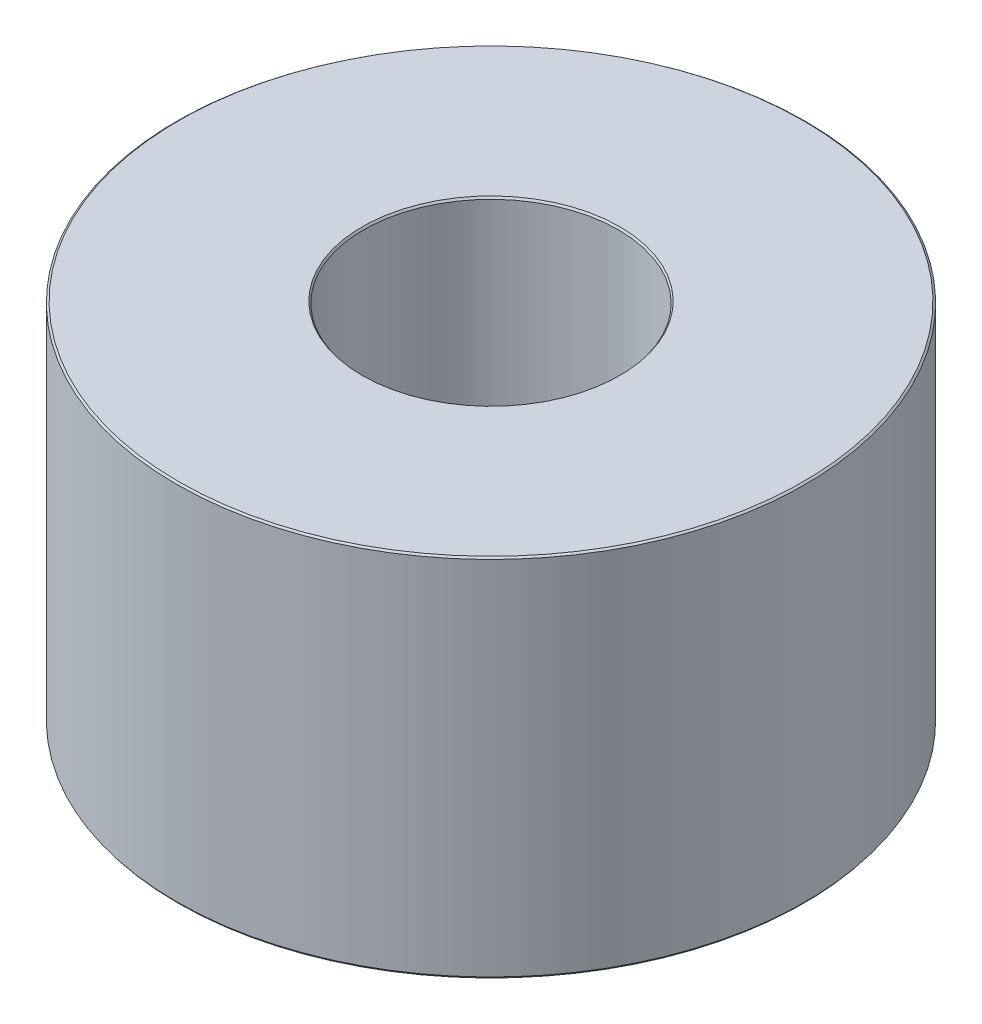
SolidWorks part; units mm, degrees
ref_plane "Front Plane" through (0, 0, 0) normal (0, 0, 1) x (1, 0, 0)
ref_plane "Top Plane" through (0, 0, 0) normal (0, 1, 0) x (1, 0, 0)
ref_plane "Right Plane" through (0, 0, 0) normal (1, 0, 0) x (0, 0, -1)
sketch "Sketch1" plane through (0, 0, 0) normal (0, 1, 0) x (1, 0, 0)
  circle A0 centre (0, 0) radius 47.5
  dimension "SLEEVE_OD" = 95
extrude "Boss-Extrude1" add sketch "Sketch1" along normal blind 55.1286
sketch "Sketch2" plane through (0, 0, 0) normal (0, 1, 0) x (1, 0, 0)
  circle A0 centre (0, 0) radius 19.2505
  dimension "BORE_D" = 38.501
extrude "Cut-Extrude1" cut sketch "Sketch2" along normal through all
chamfer "Chamfer1" distance 0.2154 angle 53.232 4 edges at (0, 55.1286, 19.2505) (0, 0, 19.2505) (0, 0, 47.5) (0, 55.1286, 47.5) first distance on face at (0, 55.1286, 19.2505) first distance on face at (0, 0, 19.2505) first distance on face at (0, 55.1286, 47.5)
